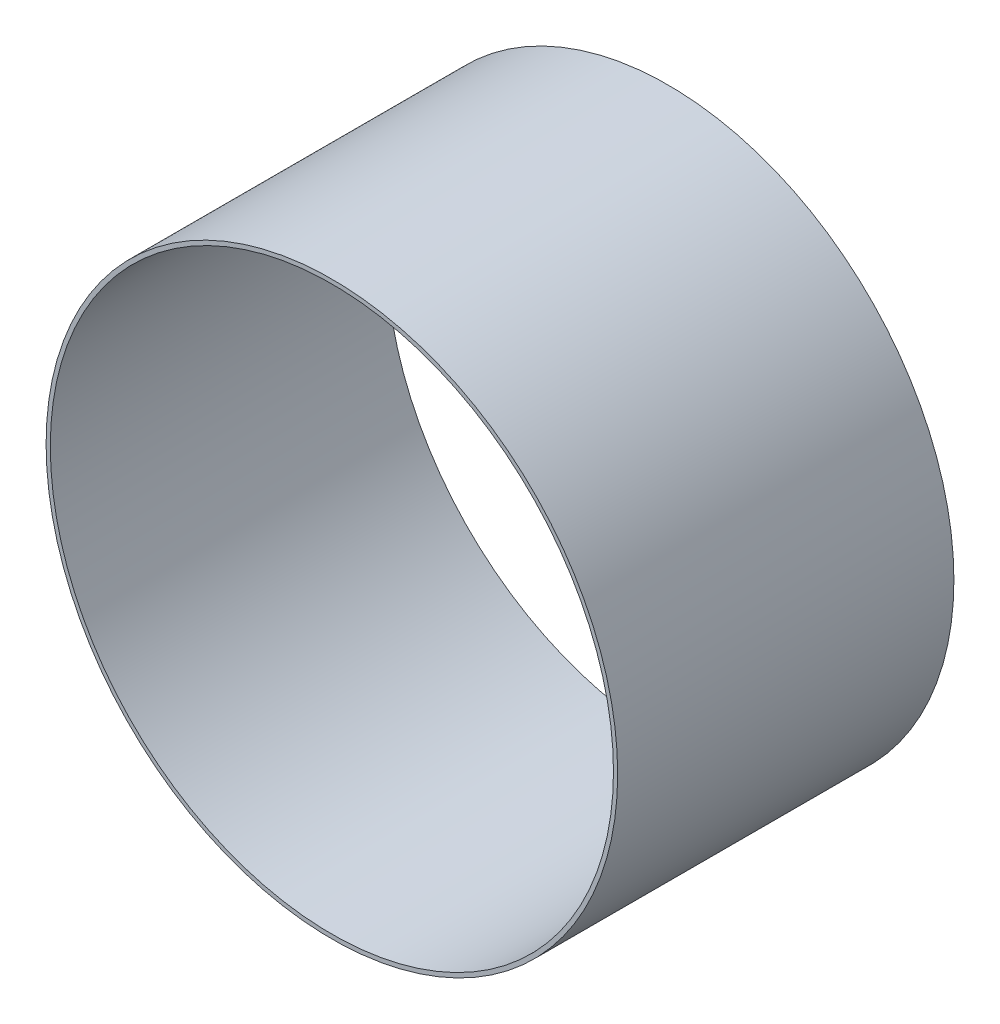
SolidWorks part; units mm, degrees
ref_plane "Front Plane" through (0, 0, 0) normal (0, 0, 1) x (1, 0, 0)
ref_plane "Top Plane" through (0, 0, 0) normal (0, 1, 0) x (1, 0, 0)
ref_plane "Right Plane" through (0, 0, 0) normal (1, 0, 0) x (0, 0, -1)
sketch "Sketch1" plane through (0, 0, 0) normal (0, 0, 1) x (1, 0, 0)
  circle A0 centre (0, 0) radius 68
  dimension "D1" = 136
extrude "Boss-Extrude1" add sketch "Sketch1" along normal blind 40 and the other way blind 40
sketch "Sketch2" plane through (0, 0, -40) normal (0, 0, -1) x (-1, 0, 0)
  circle A0 centre (0, 0) radius 67
  dimension "D1" = 134
extrude "Cut-Extrude1" cut sketch "Sketch2" against normal blind 80
equation "\"D1@Boss-Extrude1\"=136/2"
equation "\"D2@Boss-Extrude1\"=136/2"
